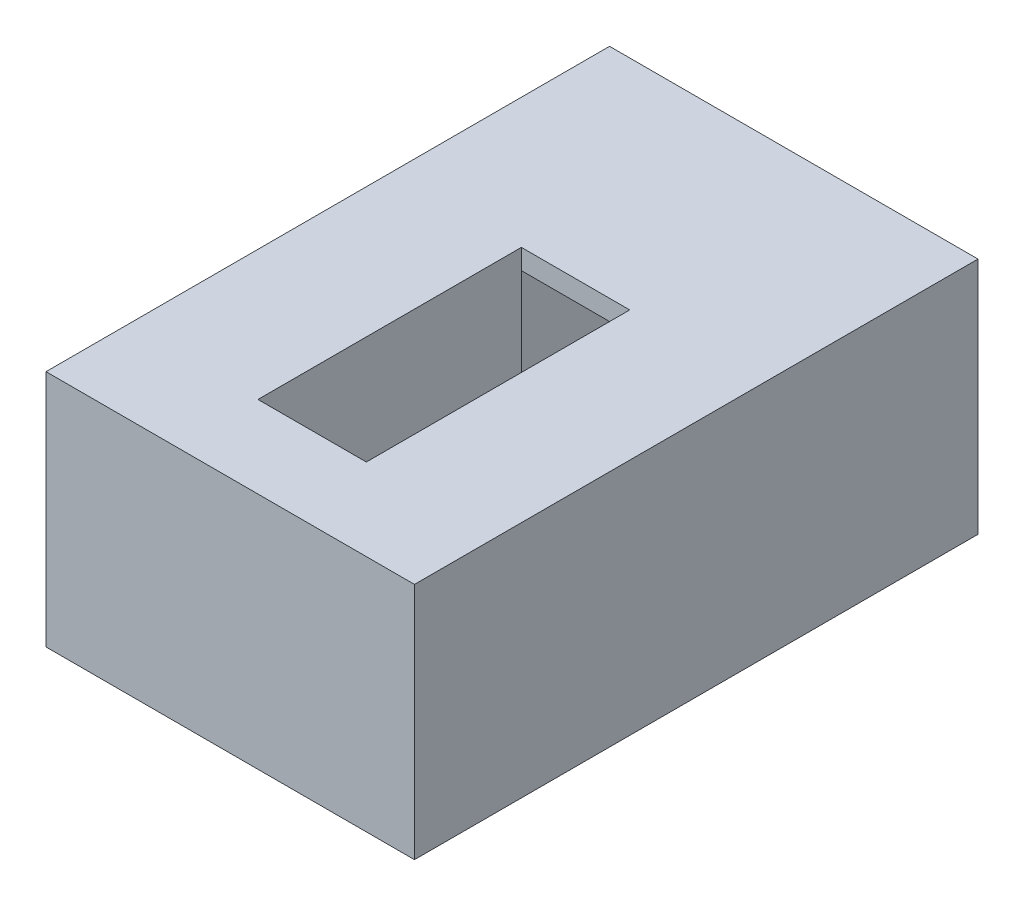
SolidWorks part; units mm, degrees
ref_plane "Спереди" through (0, 0, 0) normal (0, 0, 1) x (1, 0, 0)
ref_plane "Сверху" through (0, 0, 0) normal (0, 1, 0) x (1, 0, 0)
ref_plane "Справа" through (0, 0, 0) normal (1, 0, 0) x (0, 0, -1)
sketch "Эскиз1" plane through (0, 0, 0) normal (1, 0, 0) x (0, 0, -1)
  line L1 (-2600, 1100) -> (2600, 1100)
  line L2 (-2600, 1100) -> (-2600, -1100)
  line L3 (-2600, -1100) -> (2600, -1100)
  line L4 (2600, 1100) -> (2600, -1100)
  line L5 (-2600, 1100) -> (2600, -1100) construction
  line L6 (-2600, -1100) -> (2600, 1100) construction
  point P0 (0, 0)
extrude "Бобышка-Вытянуть1" add sketch "Эскиз1" along normal mid plane 3400
sketch "Эскиз3" plane through (0, 0, 0) normal (1, 0, 0) x (0, 0, -1)
  line L0 (-1844.1325, 930.2672) -> (-2363.5134, 930.2672)
  line L1 (-2363.5134, 930.2672) -> (-2363.5134, -219.7328)
  line L2 (-2363.5134, -219.7328) -> (586.4866, -219.7328)
  line L3 (586.4866, -219.7328) -> (586.4866, -780.2687)
  line L4 (586.4866, -780.2687) -> (2386.4866, -780.2687)
  line L5 (2386.4866, -780.2687) -> (2386.4866, 914.3685)
  line L6 (2386.4866, 914.3685) -> (586.4866, 914.3685)
  line L8 (-1844.1325, 930.2672) -> (-1844.1325, 1100)
  line L9 (2600, 1100) -> (-2600, 1100) construction
  line L10 (-1844.1325, 1100) -> (586.4866, 1100)
  line L11 (586.4866, 1100) -> (586.4866, 914.3685)
  point P0 (627.4552, 914.3685)
  dimension "D1" = 1800
  dimension "D2" = 4750
  dimension "D3" = 1150
  dimension "D4" = 1800
extrude "Вырез-Вытянуть1" cut sketch "Эскиз3" against normal mid plane 1000
sketch "Эскиз4" plane through (0, 0, 0) normal (1, 0, 0) x (0, 0, -1)
  line L0 (2386.4866, 914.3685) -> (586.4866, 914.3685) construction
  line L1 (2386.4866, 914.3685) -> (586.4866, 914.3685)
  line L2 (2386.4866, 914.3685) -> (2386.4866, -780.2687)
  line L3 (2386.4866, -780.2687) -> (586.4866, -780.2687)
  line L4 (586.4866, 914.3685) -> (586.4866, -780.2687)
  line L5 (2386.4866, -780.2687) -> (2386.4866, 914.3685) construction
extrude "Вырез-Вытянуть2" cut sketch "Эскиз4" against normal mid plane 2000
